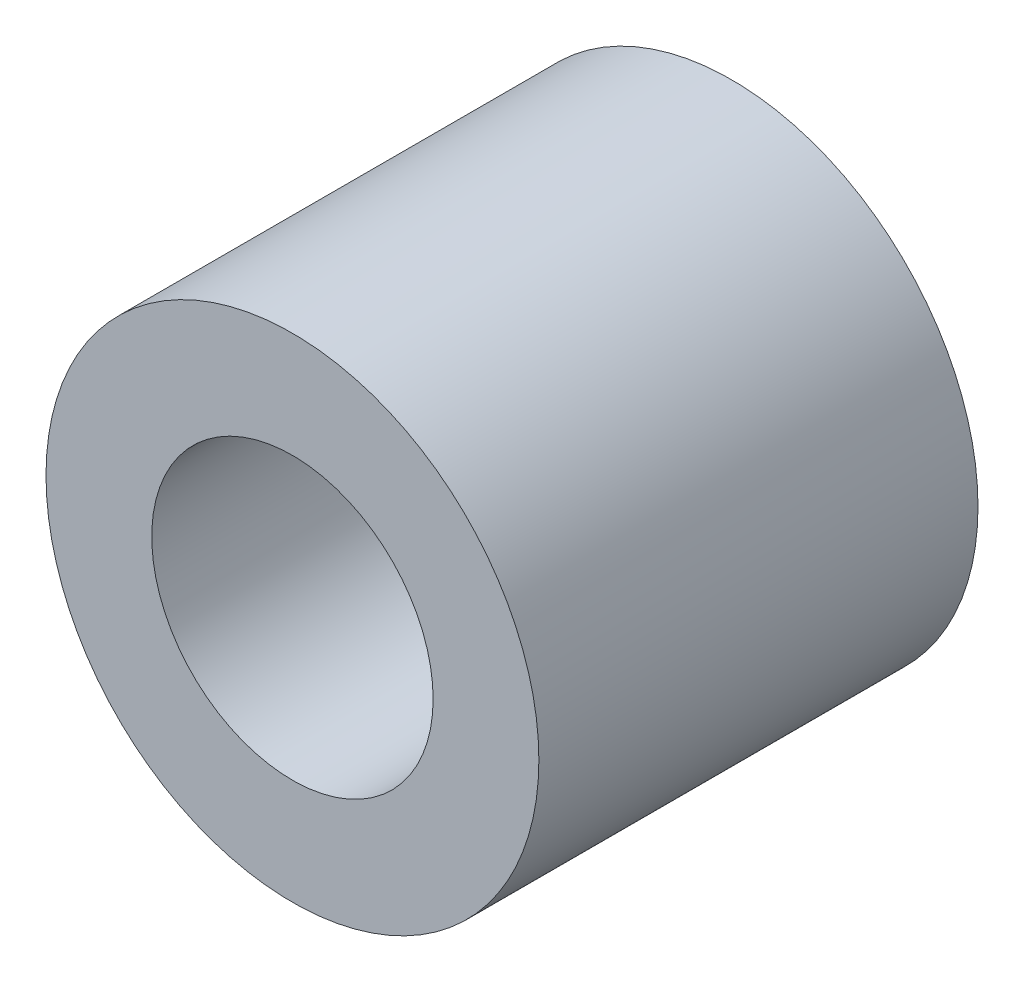
SolidWorks part; units mm, degrees
material "Iron-Copper SAE 863"
ref_plane "Front Plane" through (0, 0, 0) normal (0, 0, 1) x (1, 0, 0)
ref_plane "Top Plane" through (0, 0, 0) normal (0, 1, 0) x (1, 0, 0)
ref_plane "Right Plane" through (0, 0, 0) normal (1, 0, 0) x (0, 0, -1)
sketch "Sketch1" plane through (0, 0, 0) normal (0, 0, 1) x (1, 0, 0)
  circle A0 centre (0, 0) radius 7.015
  circle A1 centre (0, 0) radius 4.005
  dimension "ID" = 8.01
  dimension "OD" = 14.03
extrude "Boss-Extrude1" add sketch "Sketch1" along normal mid plane 12.5
sketch "Sketch2" plane through (0, 0, 0) normal (1, 0, 0) x (0, 0, -1)
  line L0 (-6.25, 7.015) -> (6.25, 7.015)
  line L1 (-6.25, 0) -> (6.25, 0) construction
  line L2 (-6.25, 7.015) -> (-6.25, -7.015) construction
  line L3 (6.25, -7.015) -> (6.25, 7.015) construction
  dimension "D1" = 14.03
  dimension "D2" = 12.5
ref_axis "Center Axis 1" through (0, 0, 4.4) along (0, 0, -1)
ref_plane "Contact Plane 1" through (0, 0, 6.25) normal (0, 0, 1) x (1, 0, 0)
ref_plane "Contact Plane 2" through (0, 0, -6.25) normal (0, 0, -1) x (-1, 0, 0)
equation "\"D1@Sketch2\"=\"OD@Sketch1\""
